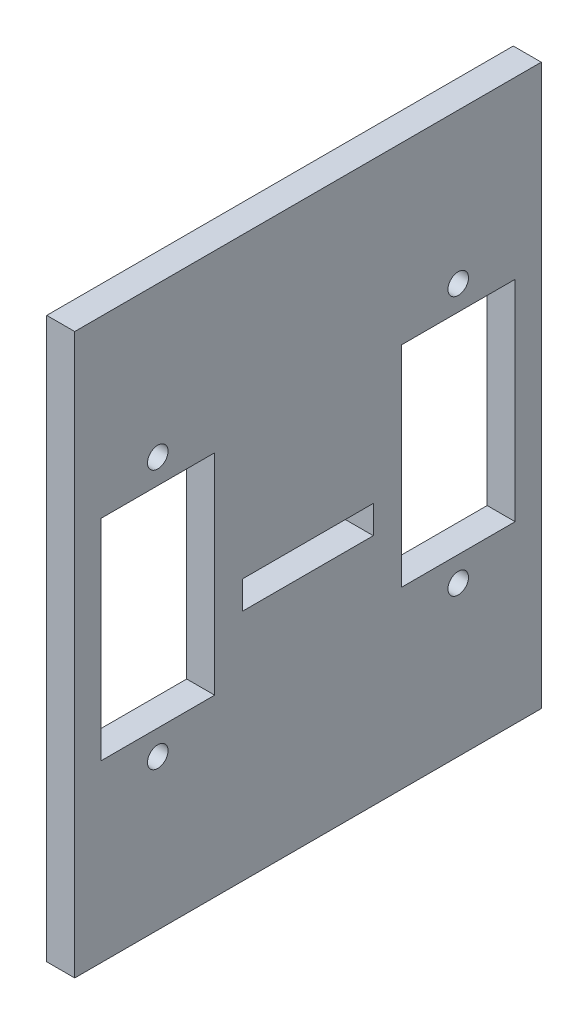
SolidWorks part; units mm, degrees
ref_plane "Front Plane" through (0, 0, 0) normal (0, 0, 1) x (1, 0, 0)
ref_plane "Top Plane" through (0, 0, 0) normal (0, 1, 0) x (1, 0, 0)
ref_plane "Right Plane" through (0, 0, 0) normal (1, 0, 0) x (0, 0, -1)
sketch "Sketch1" plane through (0, 0, 0) normal (1, 0, 0) x (0, 0, -1)
  line L0 (25, 0) -> (-25, 0) construction
  line L1 (-25, -30) -> (25, -30)
  line L2 (-25, -30) -> (-25, 30)
  line L3 (-25, 30) -> (25, 30)
  line L4 (25, -30) -> (25, 30)
  line L5 (-25, -30) -> (25, 30) construction
  line L6 (-25, 30) -> (25, -30) construction
  line L7 (0, 0) -> (10, 0) construction
  line L8 (22.2, -11.25) -> (10, -11.25)
  line L9 (22.2, -11.25) -> (22.2, 11.25)
  line L10 (22.2, 11.25) -> (10, 11.25)
  line L11 (10, -11.25) -> (10, 11.25)
  line L12 (16.1, 11.25) -> (16.1, 13.9) construction
  line L13 (0, 30) -> (0, -30) construction
  line L14 (-22.2, -11.25) -> (-10, -11.25)
  line L15 (-10, -11.25) -> (-10, 11.25)
  line L16 (-22.2, -11.25) -> (-22.2, 11.25)
  line L17 (-22.2, 11.25) -> (-10, 11.25)
  circle A0 centre (16.1, 13.9) radius 1.1
  circle A1 centre (16.1, -13.9) radius 1.1
  circle A2 centre (-16.1, -13.9) radius 1.1
  circle A3 centre (-16.1, 13.9) radius 1.1
  point P0 (0, 0)
  dimension "D6" = 2.2
  dimension "D1" = 22.5
  dimension "D2" = 12.2
  dimension "D3" = 60
  dimension "D4" = 50
  dimension "D5" = 10
  dimension "D7" = 2.65
extrude "Boss-Extrude1" add sketch "Sketch1" along normal blind 3
sketch "Sketch2" plane through (3, 0, 0) normal (1, 0, 0) x (0, 0, -1)
  line L0 (-10, 11.25) -> (10, 11.25) construction
  line L1 (0, 11.25) -> (0, -1.95) construction
  line L4 (-7, -1.95) -> (7, -1.95)
  line L5 (-7, -1.95) -> (-7, -4.95)
  line L6 (-7, -4.95) -> (7, -4.95)
  line L8 (7, -1.95) -> (7, -4.95)
  point P11 (0, -1.95)
  dimension "D1" = 13.2
  dimension "D2" = 14
  dimension "D3" = 3
extrude "Cut-Extrude1" cut sketch "Sketch2" against normal blind 3
